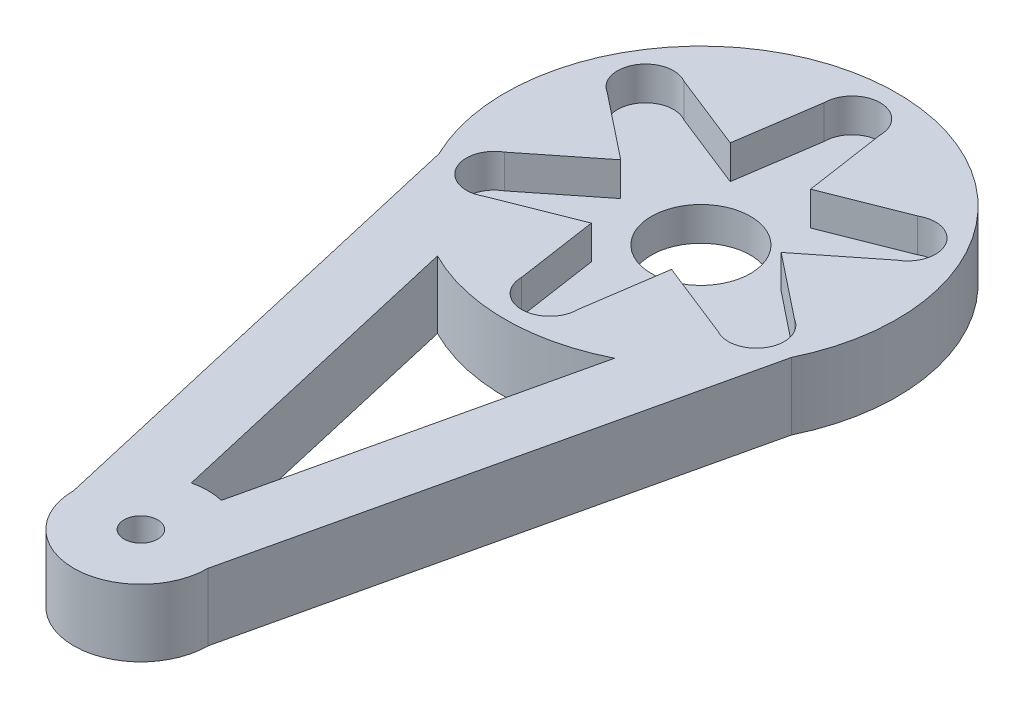
SolidWorks part; units mm, degrees
ref_plane "Front Plane" through (0, 0, 0) normal (0, 0, 1) x (1, 0, 0)
ref_plane "Top Plane" through (0, 0, 0) normal (0, 1, 0) x (1, 0, 0)
ref_plane "Right Plane" through (0, 0, 0) normal (1, 0, 0) x (0, 0, -1)
sketch "Sketch1" plane through (0, 0, 0) normal (0, 1, 0) x (1, 0, 0)
  line L0 (0, 0) -> (0, 16)
  line L2 (0, 13.5) -> (-2.5, 13.5)
  line L3 (0, 13.5) -> (2.5, 13.5)
  line L4 (-2.5, 13.5) -> (-4.5, 0)
  line L5 (2.5, 13.5) -> (4.5, 0)
  line L6 (0, 0) -> (13.8564, 8)
  line L8 (11.6913, 6.75) -> (10.4413, 8.9151)
  line L9 (11.6913, 6.75) -> (12.9413, 4.5849)
  line L10 (10.4413, 8.9151) -> (-2.25, 3.8971)
  line L11 (12.9413, 4.5849) -> (2.25, -3.8971)
  line L12 (0, 0) -> (13.8564, -8)
  line L14 (11.6913, -6.75) -> (12.9413, -4.5849)
  line L15 (11.6913, -6.75) -> (10.4413, -8.9151)
  line L16 (12.9413, -4.5849) -> (2.25, 3.8971)
  line L17 (10.4413, -8.9151) -> (-2.25, -3.8971)
  line L18 (0, 0) -> (0, -16)
  line L20 (0, -13.5) -> (2.5, -13.5)
  line L21 (0, -13.5) -> (-2.5, -13.5)
  line L22 (2.5, -13.5) -> (4.5, 0)
  line L23 (-2.5, -13.5) -> (-4.5, 0)
  line L24 (0, 0) -> (-13.8564, -8)
  line L26 (-11.6913, -6.75) -> (-10.4413, -8.9151)
  line L27 (-11.6913, -6.75) -> (-12.9413, -4.5849)
  line L28 (-10.4413, -8.9151) -> (2.25, -3.8971)
  line L29 (-12.9413, -4.5849) -> (-2.25, 3.8971)
  line L30 (0, 0) -> (-13.8564, 8)
  line L32 (-11.6913, 6.75) -> (-12.9413, 4.5849)
  line L33 (-11.6913, 6.75) -> (-10.4413, 8.9151)
  line L34 (-12.9413, 4.5849) -> (-2.25, -3.8971)
  line L35 (-10.4413, 8.9151) -> (2.25, 3.8971)
  circle A1 centre (0, 13.5) radius 2.5
  circle A3 centre (11.6913, 6.75) radius 2.5
  circle A5 centre (11.6913, -6.75) radius 2.5
  circle A7 centre (0, -13.5) radius 2.5
  circle A9 centre (-11.6913, -6.75) radius 2.5
  circle A10 centre (0, 0) radius 4.425
  circle A11 centre (-11.6913, 6.75) radius 2.5
  circle A12 centre (0, 0) radius 17.5
  point P53 (0, 0)
  dimension "D1" = 8.85
  dimension "D7" = 35
  dimension "D2" = 16
  dimension "D3" = 2.5
  dimension "D4" = 2.5
  dimension "D5" = 2.5
  dimension "D6" = 6
extrude "Boss-Extrude3" add sketch "Sketch1" along normal blind 6 contours A12 A11 L35 L4 A1 L5 L10 A3 L11 L16 A5 L17 L22 A7 L23 L28 A9 L29 L34 region at (-17.005, 0, 0)
extrude "Boss-Extrude5" add sketch "Sketch1<11>" along normal blind 3 contours L33 A11 L30 | L30 A11 L32 | L32 A11 L30 | L30 A11 L33 | A11 L30 L4 L35 | A11 L34 L29 L30 | L35 L4 L29 L10 | A10 L30 L4 L23 L24 | A10 L0 L10 L29 L30 | L29 L34 L23 L4 | A9 L24 L34 L29 | L24 A9 L27 | L27 A9 L24 | L24 A9 L26 | L26 A9 L24 | A9 L28 L23 L24 | A10 L24 L34 L17 L18 | L34 L23 L28 L17 | A7 L18 L28 L23 | A7 L22 L17 L18 | A10 L18 L28 L11 L12 | L28 L17 L22 L11 | L18 A7 L21 | L20 A7 L18 | L21 A7 L18 | L18 A7 L20 | A5 L12 L22 L17 | L15 A5 L12 | L14 A5 L12 | L12 A5 L15 | L12 A5 L14 | A5 L16 L11 L12 | A10 L12 L22 L5 L6 | L22 L11 L16 L5 | A3 L6 L16 L11 | A10 L6 L16 L35 L0 | L10 L35 L16 L5 | A3 L10 L5 L6 | L8 A3 L6 | L6 A3 L9 | L9 A3 L6 | L6 A3 L8 | A1 L0 L10 L5 | A1 L4 L35 L0 | L0 A1 L2 | L2 A1 L0 | L0 A1 L3 | L3 A1 L0 | A5 region at (-1.061, 0, -14.561) region at (1.061, 0, -12.439) region at (-1.061, 0, -12.439) region at (1.061, 0, -14.561) region at (1.6102, 0, -8.4409) region at (-1.6102, 0, -8.4409) region at (1.1071, 0, -4.2965) region at (-0.0488, 0, -4.6059) region at (-2.6346, 0, -4.5633) region at (2.6346, 0, -4.5633) region at (-6.5049, 0, -5.6149) region at (6.5049, 0, -5.6149) region at (-4.013, 0, -2.2611) region at (-5.2692, 0, 0) region at (-8.1151, 0, -2.826) region at (-10.2419, 0, -7.1384) region at (-12.0797, 0, -8.1994) region at (5.2692, 0, 0) region at (4.2749, 0, -1.1896) region at (8.1151, 0, -2.826) region at (12.0797, 0, -8.1994) region at (10.2419, 0, -7.1384) region at (-8.1151, 0, 2.826) region at (-11.303, 0, -5.3006) region at (-13.1407, 0, -6.3616) region at (11.303, 0, -5.3006) region at (8.1151, 0, 2.826) region at (13.1407, 0, -6.3616) region at (3.9644, 0, 2.3452) region at (-0.0488, 0, 4.6059) region at (-2.6346, 0, 4.5633) region at (-6.5049, 0, 5.6149) region at (-11.303, 0, 5.3006) region at (-13.1407, 0, 6.3616) region at (2.6346, 0, 4.5633) region at (6.5049, 0, 5.6149) region at (13.1407, 0, 6.3616) region at (11.303, 0, 5.3006) region at (1.6102, 0, 8.4409) region at (-1.6102, 0, 8.4409) region at (-10.2419, 0, 7.1384) region at (-12.0797, 0, 8.1994) region at (10.2419, 0, 7.1384) region at (12.0797, 0, 8.1994) region at (1.061, 0, 12.439) region at (-1.061, 0, 12.439) region at (-1.061, 0, 14.561) region at (1.061, 0, 14.561)
sketch "Sketch1<11>" plane through (0, 0, 0) normal (0, 1, 0) x (1, 0, 0) same geometry as "Sketch1"
sketch "Sketch2" plane through (0, 0, 0) normal (0, -1, 0) x (1, 0, 0)
  line L0 (0, 0) -> (0, 50)
  line L1 (-17.5, 0) -> (-6, 50)
  line L2 (-17.5, 0) -> (-11.5, 0)
  line L3 (17.5, 0) -> (11.5, 0)
  line L4 (0, 50) -> (-11.5, 0)
  line L5 (0, 50) -> (11.5, 0)
  line L6 (6, 50) -> (17.5, 0)
  circle A0 centre (0, 50) radius 1.5
  circle A1 centre (0, 50) radius 6
  circle A2 centre (0, 0) radius 17.5 construction
  circle M4 centre (0, 0) radius 17.5
  dimension "D2" = 3
  dimension "D3" = 12
  dimension "D1" = 50
  dimension "D4" = 6
  dimension "D5" = 6
extrude "Boss-Extrude6" add sketch "Sketch2" against normal blind 6 contours A1 L5 L6 M4 | A1 L1 L4 M4 | L5 A1 L4 A0 | L0 A1 L5 A0 | L4 A1 L0 A0 region at (-0.4727, 0, 45.8357) region at (0.4727, 0, 45.8357) region at (7.9388, 0, 29.3344) region at (-7.9388, 0, 29.3344) region at (-4.5622, 0, 46.368)
